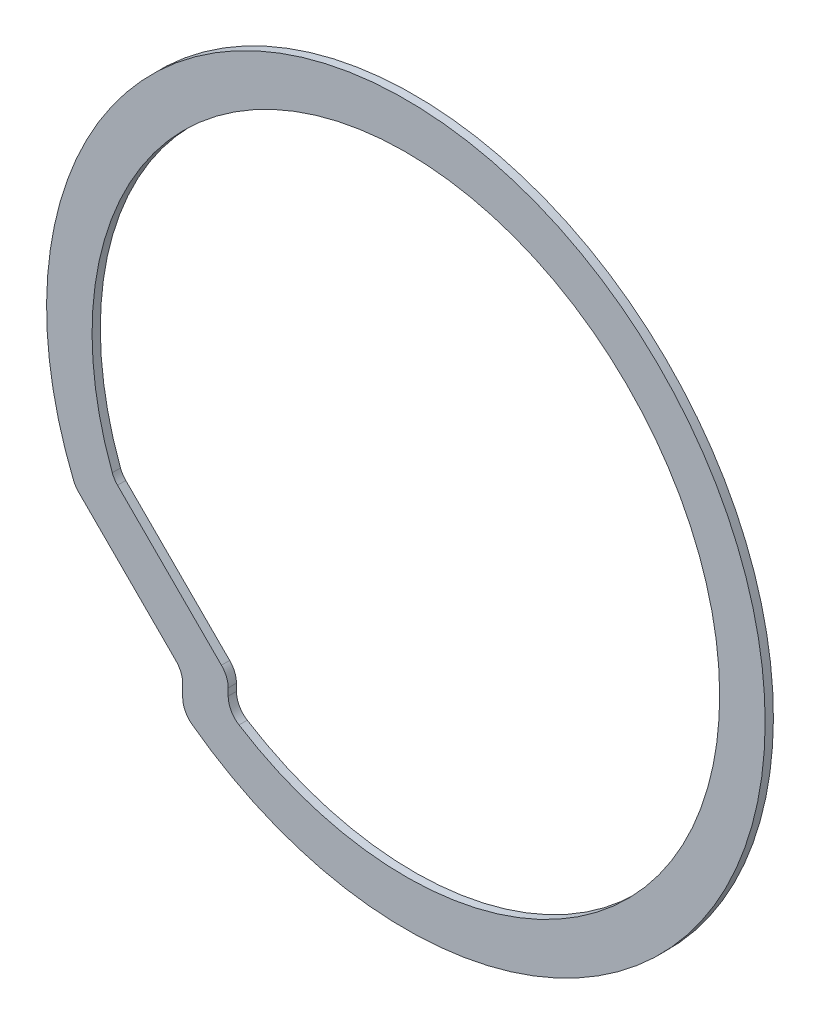
SolidWorks part; units mm, degrees
material "Balsa"
ref_plane "Front Plane" through (0, 0, 0) normal (0, 0, 1) x (1, 0, 0)
ref_plane "Top Plane" through (0, 0, 0) normal (0, 1, 0) x (1, 0, 0)
ref_plane "Right Plane" through (0, 0, 0) normal (1, 0, 0) x (0, 0, -1)
sketch "Sketch1" plane through (0, 0, 0) normal (0, 0, 1) x (1, 0, 0)
  line L0 (0, 32.094) -> (0, -346.2619) construction
  line L1 (0, 0) -> (0, 244.345) construction
  line L2 (0, 0) -> (0, 471.6969) construction
  line L3 (0, 0) -> (-283.5939, 0) construction
  line L4 (-127.2933, -32.5553) -> (-85.9841, -73.8644)
  line L5 (-85.9841, -73.8644) -> (-85.9841, -86.6438)
  line L6 (-85.9841, -73.8644) -> (-54.3993, -105.4493) construction
  arc A0 (-54.3993, -105.4493) -> (-127.2933, -32.5553) centre (0, 21.844) ccw
  arc A2 (-82.075, -89.6305) -> (-54.3993, -105.4493) centre (0, 21.844) ccw construction
  arc A3 (-127.2933, -32.5553) -> (-82.075, -89.6305) centre (0, 21.844) ccw construction
  arc A4 (-85.9841, -86.6438) -> (-54.3993, -105.4493) centre (0, 21.844) ccw
  spline S2 degree 3 poles (-1530.9406, -7642.7149) (259.0907, -1408.3953) (378.6573, 10.519) (49.9381, 150.9258) (45.7097, 152.4909) (37.1079, 155.2035) (32.7346, 156.3511) (27.1752, 157.5183) (26.0587, 157.7384) (23.8163, 158.1514) (22.6888, 158.3447) (19.306, 158.8811) (17.0511, 159.1813) (10.2867, 159.9126) (1.2693, 160.4377) (-7.745, 160.0789) (-14.5046, 159.4749) (-16.7575, 159.2176) (-20.1367, 158.7464) (-21.263, 158.5751) (-23.5156, 158.2037) (-24.6421, 158.0036) (-30.2426, 156.9366) (-34.6466, 155.8674) (-43.3063, 153.3113) (-47.562, 151.8242) (-55.9254, 148.4331) (-60.0331, 146.529) (-66.0807, 143.3516) (-68.0818, 142.2359) (-72.0044, 139.9197) (-73.9301, 138.7173) (-79.6017, 134.9792) (-86.884, 129.6473) (-93.6143, 123.6295) (-98.4521, 118.8554) (-100.0296, 117.2204) (-102.3424, 114.7015) (-103.1054, 113.8496) (-104.6077, 112.1297) (-105.3467, 111.2623) (-108.9818, 106.8875) (-111.6981, 103.2683) (-116.7574, 95.7975) (-119.1004, 91.9459) (-123.4121, 84.0098) (-125.3809, 79.9253) (-127.6006, 74.6695) (-128.0327, 73.61) (-128.8681, 71.4874) (-129.2719, 70.423) (-130.4422, 67.2205) (-131.1674, 65.0732) (-133.1812, 58.5951) (-135.4347, 49.861) (-136.834, 40.9354) (-137.5569, 34.168) (-137.7434, 31.9) (-137.9397, 28.4793) (-137.9911, 27.3374) (-138.0656, 25.0596) (-138.0887, 23.9223) (-138.135, 18.2442) (-137.9496, 13.7276) (-137.1441, 4.7454) (-136.5239, 0.2797) (-134.8456, -8.6005) (-133.7876, -13.015) (-131.2181, -21.791) (-129.7278, -26.0794) (-126.351, -34.4622) (-124.4643, -38.5569) (-120.2966, -46.5538) (-118.0156, -50.456) (-114.9122, -55.2108) (-114.2789, -56.1556) (-112.9868, -58.0327) (-112.3272, -58.9661) (-110.315, -61.7398) (-108.9333, -63.5482) (-104.6702, -68.8537) (-98.6716, -75.6089) (-92.0553, -81.7381) (-86.8592, -86.0978) (-85.0881, -87.5114) (-82.3719, -89.5716) (-81.4566, -90.2482) (-79.6058, -91.5811) (-78.6696, -92.238) (312.7351, -359.6403) (1980.7618, 1435.5712) (5240.7041, 5800.1077) knots -2.409432 -2.409432 -2.409432 -2.409432 0.03125 0.03125 0.0625 0.0625 0.09375 0.09375 0.101563 0.101563 0.109375 0.109375 0.125 0.125 0.15625 0.1875 0.1875 0.203125 0.203125 0.210937 0.210937 0.21875 0.21875 0.25 0.25 0.28125 0.28125 0.3125 0.3125 0.328125 0.328125 0.34375 0.34375 0.375 0.40625 0.40625 0.421875 0.421875 0.429687 0.429687 0.4375 0.4375 0.46875 0.46875 0.5 0.5 0.53125 0.53125 0.539062 0.539062 0.546875 0.546875 0.5625 0.5625 0.59375 0.625 0.625 0.640625 0.640625 0.648437 0.648437 0.65625 0.65625 0.6875 0.6875 0.71875 0.71875 0.75 0.75 0.78125 0.78125 0.8125 0.8125 0.84375 0.84375 0.851562 0.851562 0.859375 0.859375 0.875 0.875 0.90625 0.9375 0.9375 0.953125 0.953125 0.960937 0.960937 0.96875 0.96875 4.2021 4.2021 4.2021 4.2021 only from (66.3397, 143.1887) to (-66.0465, -100.0388)
  spline S3 degree 3 poles (66.3397, 143.1887) (62.3323, 145.3909) (58.2494, 147.3758) (49.9381, 150.9258) (45.7097, 152.4909) (37.1079, 155.2035) (32.7346, 156.3511) (27.1752, 157.5183) (26.0587, 157.7384) (23.8163, 158.1514) (22.6888, 158.3447) (19.306, 158.8811) (17.0511, 159.1813) (10.2867, 159.9126) (1.2693, 160.4377) (-7.745, 160.0789) (-14.5046, 159.4749) (-16.7575, 159.2176) (-20.1367, 158.7464) (-21.263, 158.5751) (-23.5156, 158.2037) (-24.6421, 158.0036) (-30.2426, 156.9366) (-34.6466, 155.8674) (-43.3063, 153.3113) (-47.562, 151.8242) (-55.9254, 148.4331) (-60.0331, 146.529) (-66.0807, 143.3516) (-68.0818, 142.2359) (-72.0044, 139.9197) (-73.9301, 138.7173) (-79.6017, 134.9792) (-86.884, 129.6473) (-93.6143, 123.6295) (-98.4521, 118.8554) (-100.0296, 117.2204) (-102.3424, 114.7015) (-103.1054, 113.8496) (-104.6077, 112.1297) (-105.3467, 111.2623) (-108.9818, 106.8875) (-111.6981, 103.2683) (-116.7574, 95.7975) (-119.1004, 91.9459) (-123.4121, 84.0098) (-125.3809, 79.9253) (-127.6006, 74.6695) (-128.0327, 73.61) (-128.8681, 71.4874) (-129.2719, 70.423) (-130.4422, 67.2205) (-131.1674, 65.0732) (-133.1812, 58.5951) (-135.4347, 49.861) (-136.834, 40.9354) (-137.5569, 34.168) (-137.7434, 31.9) (-137.9397, 28.4793) (-137.9911, 27.3374) (-138.0656, 25.0596) (-138.0887, 23.9223) (-138.135, 18.2442) (-137.9496, 13.7276) (-137.1441, 4.7454) (-136.5239, 0.2797) (-134.8456, -8.6005) (-133.7876, -13.015) (-131.2181, -21.791) (-129.7278, -26.0794) (-127.6847, -31.1513) (-127.3213, -32.0275) (-126.9491, -32.8995) knots 0 0 0 0 0.03125 0.03125 0.0625 0.0625 0.09375 0.09375 0.101563 0.101563 0.109375 0.109375 0.125 0.125 0.15625 0.1875 0.1875 0.203125 0.203125 0.210937 0.210937 0.21875 0.21875 0.25 0.25 0.28125 0.28125 0.3125 0.3125 0.328125 0.328125 0.34375 0.34375 0.375 0.40625 0.40625 0.421875 0.421875 0.429687 0.429687 0.4375 0.4375 0.46875 0.46875 0.5 0.5 0.53125 0.53125 0.539062 0.539062 0.546875 0.546875 0.5625 0.5625 0.59375 0.625 0.625 0.640625 0.640625 0.648437 0.648437 0.65625 0.65625 0.6875 0.6875 0.71875 0.71875 0.75 0.75 0.78125 0.78125 0.787815 0.787815 0.787815 0.787815 construction
  point P2 (0, 160.2226)
  point P3 (0, -116.9127)
  point P23 (-85.9841, -73.8644)
  dimension "D1" = 277.1353
  dimension "D2" = 276.86
  dimension "D3" = 21.844
  dimension "D5" = 45
  dimension "D6" = 113.03
  dimension "D4" = 58.42
  dimension "D7" = 45
extrude "Boss-Extrude1" add sketch "Sketch1" along normal mid plane 3.175
sketch "Sketch2" plane through (0, 0, 1.5875) normal (0, 0, 1) x (1, 0, 0)
  line L4 (-112.4231, -22.6399) -> (-68.4581, -66.6049)
  line L5 (-68.4581, -66.6049) -> (-68.4581, -77.8117)
  line L6 (-112.4231, -22.6399) -> (-68.4581, -66.6049)
  line L7 (-68.4581, -66.6049) -> (-68.4581, -77.8117)
  arc A2 (-68.4581, -77.8117) -> (-112.4231, -22.6399) centre (0, 21.844) ccw
  arc A3 (-68.4581, -77.8117) -> (-112.4231, -22.6399) centre (0, 21.844) ccw
  dimension "D1" = 17.526
extrude "Cut-Extrude1" cut sketch "Sketch2" against normal up to surface (3.175 mm away) up to face at (-27.5361, -9.1994, -1.5875)
fillet "Fillet1" radius 8.89 6 edges at (-127.2933, -32.5553, 0) (-112.4231, -22.6399, 0) (-85.9841, -73.8644, 0) (-85.9841, -86.6438, 0) (-68.4581, -66.6049, 0) (-68.4581, -77.8117, 0)
sketch "Sketch3" plane through (0, 0, 1.5875) normal (0, 0, 1) x (1, 0, 0)
  line L0 (-0.0002, 49.9919) -> (-0.0176, 733.2) construction
  line L1 (-0.0002, 49.9919) -> (-0.0176, 733.2) construction
  line L2 (-136.2041, -28.3557) -> (-0.0002, 49.9919) construction
  line L3 (136.2076, -28.3488) -> (-0.0002, 49.9919) construction
  line L4 (-136.2041, -28.3557) -> (-0.0002, 49.9919) construction
  line L5 (136.2076, -28.3488) -> (-0.0002, 49.9919) construction
  line L6 (-1.6539, 152.6441) -> (-1.654, 160.2641)
  line L7 (1.6481, 152.6442) -> (1.648, 160.2642)
  line L8 (-1.6539, 152.6441) -> (1.6481, 152.6442)
  line L9 (121.7113, -43.3617) -> (108.5007, -35.7073)
  line L10 (120.1169, -46.1175) -> (106.9045, -38.4621)
  line L11 (-126.0584, -33.7901) -> (-88.588, -71.2606)
  line L12 (-85.9841, -77.5468) -> (-85.9841, -82.2574)
  line L13 (-126.0584, -33.7901) -> (-88.588, -71.2606) construction
  line L14 (-85.9841, -77.5468) -> (-85.9841, -82.2574) construction
  line L30 (-123.167, -47.8929) -> (-106.3545, -38.1503)
  line L39 (120.1169, -46.1175) -> (106.9045, -38.4621) construction
  line L42 (121.7113, -43.3617) -> (108.5007, -35.7073) construction
  line L47 (108.5007, -35.7073) -> (120.1169, -46.1175) construction
  line L48 (114.3088, -40.9124) -> (126.5619, -48.0121) construction
  line L49 (113.8577, -42.5592) -> (122.0137, -47.2849)
  line L50 (115.5132, -39.7021) -> (123.6691, -44.4278)
  line L51 (113.8577, -42.5592) -> (115.5132, -39.7021)
  line L52 (122.0137, -47.2849) -> (123.6691, -44.4278)
  line L58 (-124.7703, -45.1423) -> (-107.9499, -35.3951)
  line L59 (-124.7703, -45.1423) -> (-123.167, -47.8929)
  line L71 (-124.7703, -45.1423) -> (-123.167, -47.8929) construction
  line L72 (-124.7703, -45.1423) -> (-107.9499, -35.3951) construction
  line L73 (-123.167, -47.8929) -> (-106.3545, -38.1503) construction
  line L74 (-123.167, -47.8929) -> (-107.9499, -35.3951) construction
  line L75 (-115.5584, -41.644) -> (-110.9064, -38.9482) construction
  line L76 (-119.3826, -41.9518) -> (-112.6266, -38.0369)
  line L77 (-117.727, -44.8088) -> (-110.971, -40.8938)
  line L78 (-119.3826, -41.9518) -> (-117.727, -44.8088)
  line L79 (-112.6266, -38.0369) -> (-110.971, -40.8938)
  arc A0 (-54.3993, -105.4493) -> (-127.2933, -32.5553) centre (0, 21.844) ccw construction
  arc A2 (-1.654, 160.2641) -> (-130.2816, -24.9489) centre (0, 21.844) ccw construction
  arc A3 (-130.2816, -24.9489) -> (-127.2933, -32.5553) centre (0, 21.844) ccw construction
  arc A4 (-1.654, 160.2641) -> (-130.2816, -24.9489) centre (0, 21.844) ccw construction
  arc A5 (-130.2816, -24.9489) -> (-127.9919, -30.8906) centre (0, 21.844) ccw construction
  arc A6 (-82.3849, -89.4016) -> (-127.9919, -30.8906) centre (0, 21.844) ccw
  arc A7 (-127.9919, -30.8906) -> (-126.0584, -33.7901) centre (-119.7722, -27.504) ccw
  arc A8 (-85.9841, -77.5468) -> (-88.588, -71.2606) centre (-94.8741, -77.5468) ccw
  arc A9 (-85.9841, -82.2574) -> (-82.3849, -89.4016) centre (-77.0941, -82.2574) ccw
  arc A11 (-127.9919, -30.8906) -> (-126.0584, -33.7901) centre (-119.7722, -27.504) ccw construction
  arc A12 (-85.9841, -77.5468) -> (-88.588, -71.2606) centre (-94.8741, -77.5468) ccw construction
  arc A13 (-85.9841, -82.2574) -> (-82.3849, -89.4016) centre (-77.0941, -82.2574) ccw construction
  arc A14 (130.2841, -24.9419) -> (1.648, 160.2642) centre (0, 21.844) ccw construction
  arc A15 (1.648, 160.2642) -> (-1.654, 160.2641) centre (0, 21.844) ccw
  arc A16 (130.2841, -24.9419) -> (1.648, 160.2642) centre (0, 21.844) ccw construction
  arc A17 (1.648, 160.2642) -> (-1.654, 160.2641) centre (0, 21.844) ccw
  spline S0 degree 3 poles (-1889.1702, -3462.4496) (-538.7125, -1203.9872) (801.3092, 1112.1831) (2081.6478, 3400.9321) knots -1255.334249 -1255.334249 -1255.334249 -1255.334249 1258.275552 1258.275552 1258.275552 1258.275552 weights 1.009259 0.996904 0.996914 1.009288 only from (120.1169, -46.1175) to (121.7113, -43.3617)
  spline S1 degree 3 poles (106.9045, -38.4621) (107.4366, -37.5438) (107.9687, -36.6256) (108.5007, -35.7073) knots 0 0 0 0 1 1 1 1 weights 1 1 1 1 construction
  spline S3 degree 3 poles (-1103.1888, 1695.5005) (-443.6399, 540.3172) (225.3722, -615.0906) (899.4021, -1763.0447) knots -628.279862 -628.279862 -628.279862 -628.279862 629.068292 629.068292 629.068292 629.068292 weights 1.001665 0.999445 0.999445 1.001664 only from (-107.9499, -35.3951) to (-106.3545, -38.1503)
  spline S4 degree 3 poles (-107.9499, -35.3951) (-107.4181, -36.3135) (-106.8863, -37.2319) (-106.3545, -38.1503) knots 0 0 0 0 1 1 1 1 weights 1 1 1 1 construction
  spline S6 degree 3 poles (-899.493, -1762.3719) (-225.1369, -615.8727) (444.2708, 539.4429) (1103.5652, 1694.6628) knots -628.1873 -628.1873 -628.1873 -628.1873 629.159659 629.159659 629.159659 629.159659 weights 1.001932 0.999356 0.999356 1.001932 only from (106.9045, -38.4621) to (108.5007, -35.7073)
  point P49 (-116.0256, -43.8229)
  point P50 (120.451, -46.3794)
  arc M19 (-82.3849, -89.4016) -> (-127.9919, -30.8906) centre (0, 21.844) ccw
  line M21 (-126.0584, -33.7901) -> (-88.588, -71.2606)
  dimension "D1" = 3.302
  dimension "D2" = 7.62
  dimension "D4" = 3.302
  dimension "D5" = 7.62
  dimension "D6" = 3.302
  dimension "D7" = 5.842
  dimension "D3" = 0
extrude "Cut-Extrude2" [suppressed] cut sketch "Sketch3" against normal through all contours L79 L76 L77 M21 | L6 L8 L7 M19 | L51 L49 L50 M19
equation "\"a\"= 0.06"
equation "\"slotwidth\"=0.13"
equation "\"slotheight\"=0.3"
